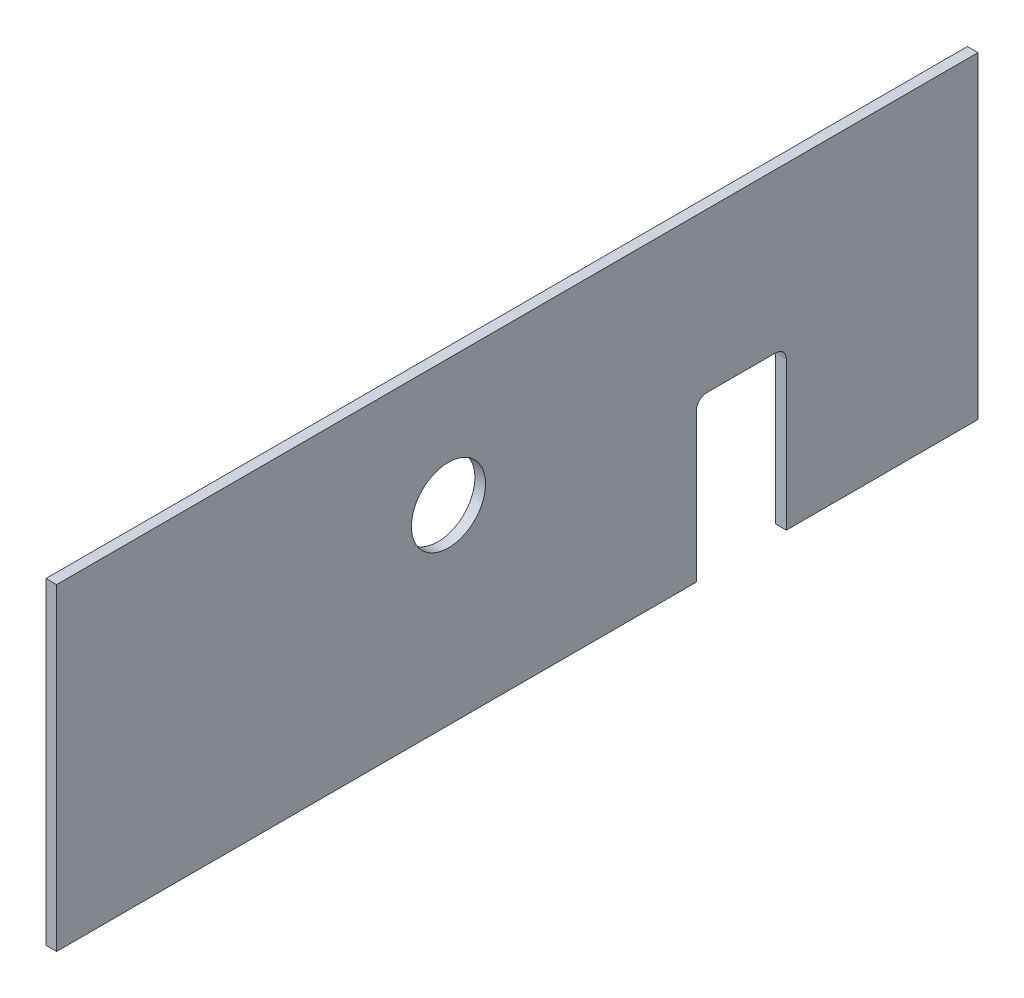
SolidWorks part; units mm, degrees
ref_plane "Front Plane" through (0, 0, 0) normal (0, 0, 1) x (1, 0, 0)
ref_plane "Top Plane" through (0, 0, 0) normal (0, 1, 0) x (1, 0, 0)
ref_plane "Right Plane" through (0, 0, 0) normal (1, 0, 0) x (0, 0, -1)
sketch "Sketch1" plane through (0, 0, 0) normal (1, 0, 0) x (0, 0, -1)
  line L1 (-43.5, -15) -> (43.5, -15)
  line L2 (-43.5, -15) -> (-43.5, 15)
  line L3 (-43.5, 15) -> (43.5, 15)
  line L4 (43.5, -15) -> (43.5, 15)
  line L5 (-43.5, -15) -> (43.5, 15) construction
  line L6 (-43.5, 15) -> (43.5, -15) construction
  line L7 (16.9, -15) -> (25.4, -15)
  line L8 (16.9, -15) -> (16.9, 0)
  line L9 (16.9, 0) -> (25.4, 0)
  line L10 (25.4, -15) -> (25.4, 0)
  circle A0 centre (-6.5, 3) radius 3.5
  point P0 (0, 0)
  point P11 (0, 0)
  dimension "D6" = 37
  dimension "D7" = 7
  dimension "D8" = 18
  dimension "D1" = 30
  dimension "D2" = 87
  dimension "D3" = 8.5
  dimension "D4" = 15
  dimension "D5" = 18.1
extrude "Boss-Extrude1" add sketch "Sketch1" along normal blind 1 contours L10 L1 L4 L3 L2 L8 L9 region at (0, 0.344, 1.001)
fillet "Fillet1" radius 1 2 edges at (0.5, 0, -16.9) (0.5, 0, -25.4)
